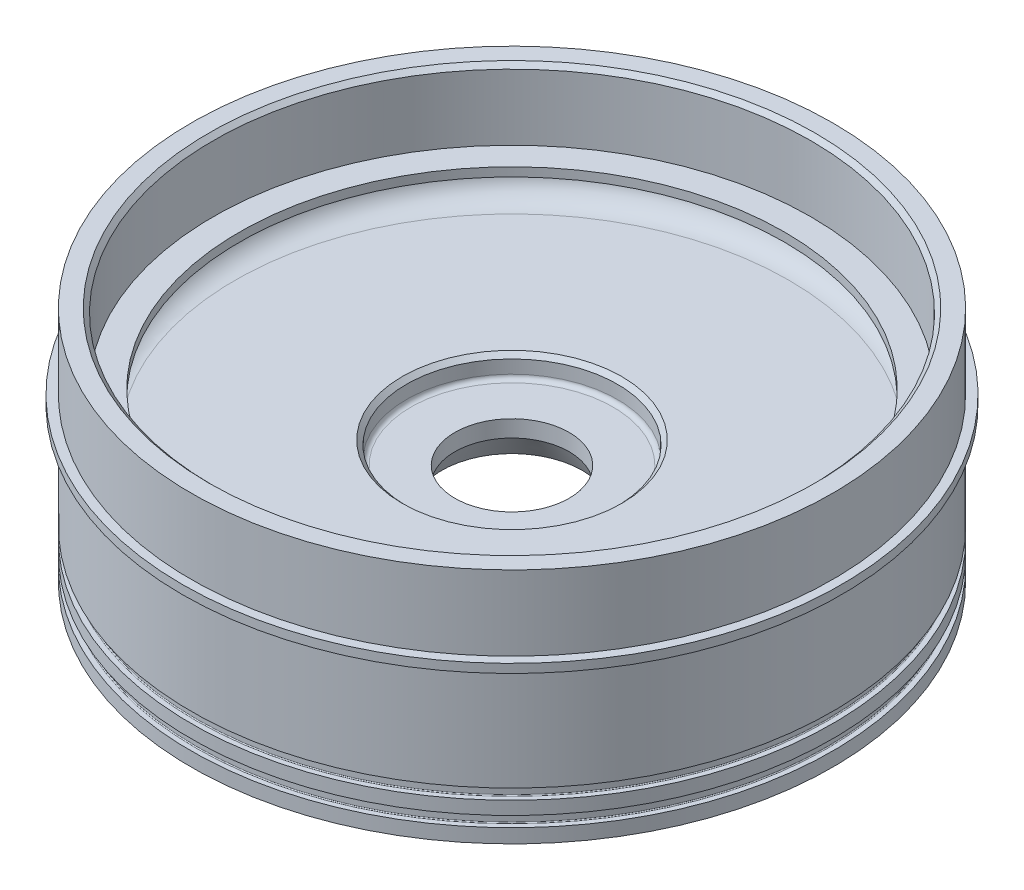
SolidWorks part; units mm, degrees
material "6061-T6 (SS)"
ref_plane "Piano frontale" through (0, 0, 0) normal (0, 0, 1) x (1, 0, 0)
ref_plane "Piano superiore" through (0, 0, 0) normal (0, 1, 0) x (1, 0, 0)
ref_plane "Piano destro" through (0, 0, 0) normal (1, 0, 0) x (0, 0, -1)
sketch "Schizzo1" plane through (0, 0, 0) normal (0, 0, 1) x (1, 0, 0)
  line L0 (0, 0) -> (0, 25.5769) construction
  line L1 (-13, 0) -> (-73, 0)
  line L2 (-73, 0) -> (-73, 14)
  line L3 (-73, 14) -> (-24, 14)
  line L4 (-24, 14) -> (-24, 9)
  line L5 (-24, 9) -> (-13, 9)
  line L6 (-13, 9) -> (-13, 0)
  line L7 (-24, 14) -> (-13, 14)
  line L8 (-13, 14) -> (-13, 9)
  line L9 (-73, 14) -> (-73, 40)
  line L10 (-73, 40) -> (-68, 40)
  line L11 (-69, 0) -> (-69, -14)
  line L12 (-69, -14) -> (-73, -14)
  line L13 (-73, -14) -> (-73, 0)
  line L14 (-68, 14) -> (-68, 40)
  line L15 (-73, 23) -> (-75, 23)
  line L16 (-75, 23) -> (-75, 21)
  line L17 (-73, -14) -> (-73, 0)
  line L18 (-73, -3) -> (-71.7, -3)
  line L19 (-71.7, -3) -> (-71.7, -5.4)
  line L20 (-71.7, -5.4) -> (-73, -5.4)
  line L21 (-73, -8.4) -> (-71.7, -8.4)
  line L22 (-71.7, -8.4) -> (-71.7, -10.8)
  line L23 (-71.7, -10.8) -> (-73, -10.8)
  line L24 (-75, 21) -> (-73, 21)
  line L25 (-68, 24) -> (-62, 24)
  line L26 (-62, 24) -> (-62, 22)
  line L27 (-62, 22) -> (-68, 22)
  dimension "D1" = 5
  dimension "D2" = 146
  dimension "D3" = 26
  dimension "D4" = 48
  dimension "D5" = 14
  dimension "D6" = 4
  dimension "D7" = 2.4
  dimension "D8" = 1.3
  dimension "D9" = 3
  dimension "D10" = 3
  dimension "D11" = 14
  dimension "D12" = 26
  dimension "D13" = 136
  dimension "D14" = 2
  dimension "D15" = 150
  dimension "D16" = 35
  dimension "D17" = 2
  dimension "D18" = 124
  dimension "D19" = 16
revolve "Rivoluzione1" add sketch "Schizzo1" angle 360 about L0 region at (-44.7166, 6.6847, 0) region at (-70.8307, -7.0125, 0) region at (-18.5, 11.5, 0) region at (-70.5, 27, 0) region at (-74, 22, 0) region at (-65, 23, 0)
chamfer "Smusso1" distance 3 angle 60 1 edges at (0, 0, -13) first distance on face at (0, 0, -69)
chamfer "Smusso2" distance 1 angle 45 1 edges at (0, -14, -69)
fillet "Raccordo1" radius 26 1 edges at (0, 0, -69)
chamfer "Smusso3" distance 1 angle 45 1 edges at (0, 40, -68)
fillet "Raccordo2" radius 0.2 4 edges at (0, -8.4, -71.7) (0, -10.8, -71.7) (0, -3, -71.7) (0, -5.4, -71.7)
sketch "Schizzo2" plane through (0, 0, 0) normal (0, 0, 1) x (1, 0, 0)
  line L0 (0, 0) -> (0, 58.1242) construction
  line L1 (0, 0) -> (-27.2443, 0) construction
  line L2 (-46.4833, 0) -> (46.4833, 0) construction
  line L3 (-13, 9) -> (-24, 9)
  line L4 (-24, 9) -> (-24, 14)
  line L6 (-24, 14) -> (-13, 14)
  line L7 (13, 14) -> (-13, 14) construction
  line L8 (-13, 14) -> (-13, 9)
  line L9 (-13, 9) -> (-13, 0) construction
  point P14 (0, 0)
  point P17 (0, 0)
  dimension "D1" = 5
  dimension "D2" = 48
revolve "Taglia-Rivoluzione1" cut sketch "Schizzo2" angle 360 about L0
fillet "Raccordo3" radius 1 1 edges at (0, 9, -24)
chamfer "Smusso4" distance 1 angle 45 1 edges at (0, 14, -24)
fillet "Raccordo4" radius 5 1 edges at (0, 14, -68)
